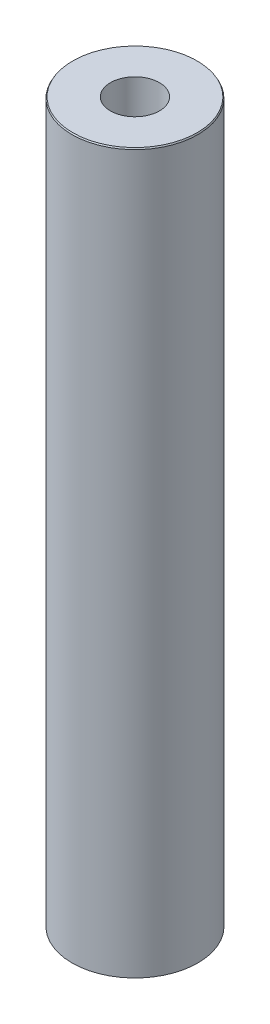
SolidWorks part; units mm, degrees
ref_plane "Front Plane" through (0, 0, 0) normal (0, 0, 1) x (1, 0, 0)
ref_plane "Top Plane" through (0, 0, 0) normal (0, 1, 0) x (1, 0, 0)
ref_plane "Right Plane" through (0, 0, 0) normal (1, 0, 0) x (0, 0, -1)
sketch "Sketch1" plane through (0, 0, 0) normal (0, 1, 0) x (1, 0, 0)
  circle A0 centre (0, 0) radius 52.5
  dimension "SHAFT_OD" = 105
extrude "Boss-Extrude1" add sketch "Sketch1" along normal blind 600
sketch "Sketch2" plane through (0, 0, 0) normal (0, 1, 0) x (1, 0, 0)
  circle A0 centre (0, 0) radius 20.4408
  dimension "BORE_D" = 40.8816
extrude "Cut-Extrude1" cut sketch "Sketch2" along normal through all
chamfer "Chamfer1" distance 1.0766 angle 30 2 edges at (0, 600, 52.5) (0, 0, 52.5) first distance on face at (0, 600, 52.5) first distance on face at (0, 0, 20.4408)
